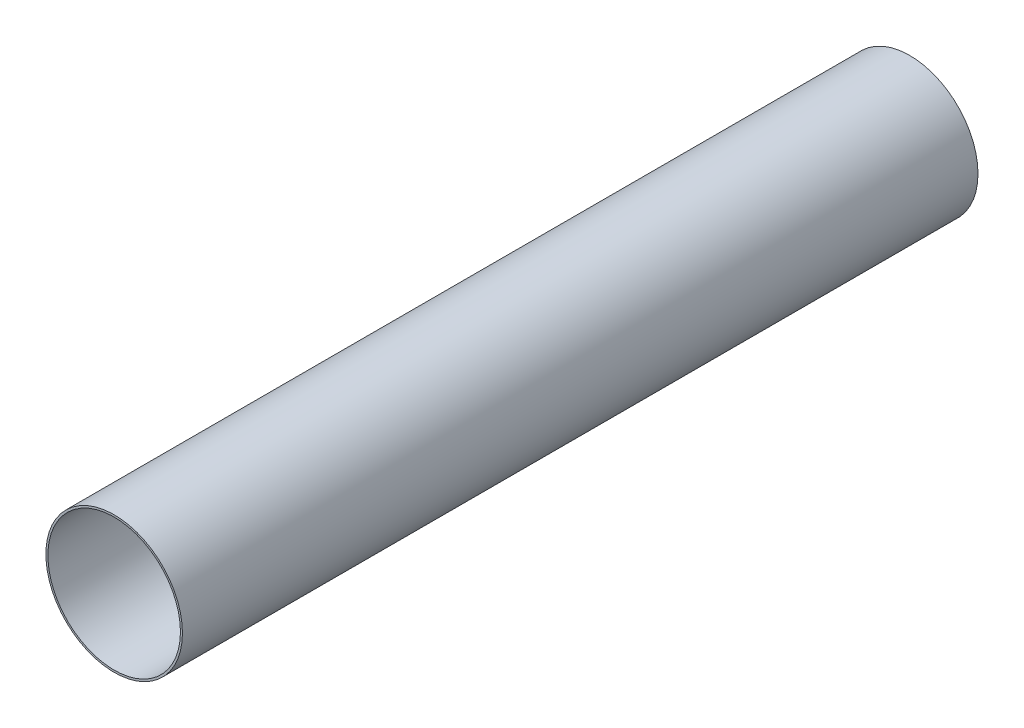
SolidWorks part; units mm, degrees
ref_plane "Front Plane" through (0, 0, 0) normal (0, 0, 1) x (1, 0, 0)
ref_plane "Top Plane" through (0, 0, 0) normal (0, 1, 0) x (1, 0, 0)
ref_plane "Right Plane" through (0, 0, 0) normal (1, 0, 0) x (0, 0, -1)
sketch "Sketch1" plane through (0, 0, 0) normal (0, 0, 1) x (1, 0, 0)
  circle A0 centre (0, 0) radius 65.405
  circle A1 centre (0, 0) radius 63.5
  dimension "D1" = 127
  dimension "D2" = 130.81
extrude "Boss-Extrude1" add sketch "Sketch1" along normal mid plane 762
equation "\"AIRFRAME_OD\"= 5.15in"
equation "\"AIRFRAME_ID\"= 5.00in"
equation "\"FLAT_T\"= 0.125in"
equation "\"NOSE_EXP_L\"= 27in"
equation "\"NOSE_SHOULDER_L\"= 5in"
equation "\"MAIN_L\"= 30in"
equation "\"RECO_COUP_L\"= 10in"
equation "\"RECO_SWITCH_L\"= 2in"
equation "\"DROGUE_L\"= 20in"
equation "\"ATS_FORE_COUP_L\"= 5.5in"
equation "\"ATS_AFT_COUP_L\"= 4.5in"
equation "\"LOWER_L\"= 30in"
equation "\"FIN_N\"= 4"
equation "\"CR_AFT_X\"= 0.5in"
equation "\"CR_FORE_X\"= 9.25in"
equation "\"D1@Sketch1\"=\"AIRFRAME_ID\""
equation "\"D2@Sketch1\"=\"AIRFRAME_OD\""
equation "\"D1@Boss-Extrude1\"=\"MAIN_L\""
equation "\"FIN_ROOT\"= 5in"
equation "\"FIN_X\"= 0.75in"
equation "\"MOTOR_OD\"= 3.091in"
equation "\"MOTOR_ID\"= 3.00in"
equation "\"COUPLER_OD\"= 4.998in"
equation "\"COUPLER_ID\"= 4.88in"
equation "\"RECO_ROD_X\"= 3.5in"
equation "\"ATS_ROD_X\"= 3in"
equation "\"MOTOR_L\"= 14in"
equation "\"MOTOR_LOWER_X\"= 2in"
